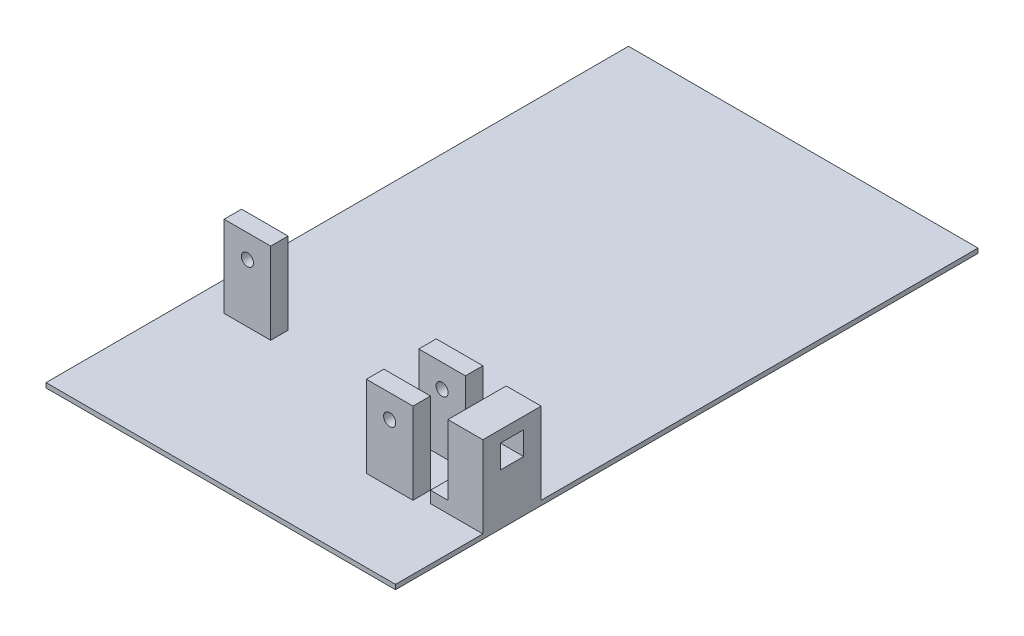
SolidWorks part; units mm, degrees
ref_plane "Front Plane" through (0, 0, 0) normal (0, 0, 1) x (1, 0, 0)
ref_plane "Top Plane" through (0, 0, 0) normal (0, 1, 0) x (1, 0, 0)
ref_plane "Right Plane" through (0, 0, 0) normal (1, 0, 0) x (0, 0, -1)
sketch "Sketch1" plane through (0, 0, 0) normal (0, 1, 0) x (1, 0, 0)
  line L0 (150, 500) -> (150, 0)
  line L1 (0, 0) -> (300, 0)
  line L2 (0, 0) -> (0, 500)
  line L3 (0, 500) -> (300, 500)
  line L4 (300, 0) -> (300, 500)
  line L5 (0, 100) -> (300, 100) construction
  line L6 (300, 125) -> (255, 125)
  line L7 (300, 125) -> (300, 75)
  line L8 (300, 75) -> (255, 75)
  line L9 (255, 125) -> (255, 75)
  line L10 (300, 125) -> (270, 125)
  line L11 (300, 125) -> (300, 75)
  line L12 (300, 75) -> (270, 75)
  line L13 (270, 125) -> (270, 75)
  point P16 (255, 100)
  dimension "D1" = 300
  dimension "D2" = 500
  dimension "D3" = 30
  dimension "D4" = 50
  dimension "D5" = 45
  dimension "D6" = 100
extrude "Boss-Extrude1" add sketch "Sketch1" along normal blind 4 contours L5 L2 L1 L0 | L2 L5 L0 L3 | L0 L5 L9 L6 L4 L3 | L9 L5 L13 L6 | L13 L5 L11 L6 | L5 L0 L1 L4 L8 L9 | L5 L9 L8 L13 | L5 L13 L8 L4 region at (223.9968, 0, -303.5828) region at (75, 0, -300) region at (220.7432, 0, -46.9595) region at (75, 0, -50) region at (262.5, 0, -112.5) region at (262.5, 0, -87.5) region at (285, 0, -112.5) region at (285, 0, -87.5)
extrude "Boss-Extrude2" add sketch "Sketch1<4>" along normal blind 10 from surface contours L9 L5 L13 L6 | L5 L9 L8 L13 | L5 L13 L8 L4 | L13 L5 L11 L6 region at (262.5, 0, -112.5) region at (262.5, 0, -87.5) region at (285, 0, -112.5) region at (285, 0, -87.5) starting at face at (150, 4, -250)
sketch "Sketch1<4>" plane through (0, 0, 0) normal (0, 1, 0) x (1, 0, 0) same geometry as "Sketch1"
extrude "Boss-Extrude3" add sketch "Sketch1<5>" along normal blind 60 from surface contours L6 L13 L8 L4 | L13 L5 L11 L6 region at (285, 0, -112.5) region at (285, 0, -87.5) starting at face at (277.5, 14, -100)
sketch "Sketch1<5>" plane through (0, 0, 0) normal (0, 1, 0) x (1, 0, 0) same geometry as "Sketch1"
sketch "Sketch15" plane through (0, 0, 0) normal (0, 1, 0) x (1, 0, 0)
  line L0 (0, 100) -> (300, 100) construction
  line L1 (245, 130) -> (205, 130)
  line L2 (245, 130) -> (245, 70)
  line L3 (245, 70) -> (205, 70)
  line L4 (205, 130) -> (205, 70)
  line L5 (245, 130) -> (205, 70) construction
  line L6 (245, 70) -> (205, 130) construction
  line L7 (255, 125) -> (255, 75) construction
  line L8 (205, 85) -> (245, 85)
  line L9 (205, 85) -> (205, 115)
  line L10 (205, 115) -> (245, 115)
  line L11 (245, 85) -> (245, 115)
  line L12 (205, 85) -> (245, 115) construction
  line L13 (205, 115) -> (245, 85) construction
  line L15 (25, 142.8667) -> (65, 142.8667)
  line L16 (25, 142.8667) -> (25, 82.8667)
  line L17 (25, 82.8667) -> (65, 82.8667)
  line L18 (65, 142.8667) -> (65, 82.8667)
  line L19 (25, 142.8667) -> (65, 82.8667) construction
  line L20 (25, 82.8667) -> (65, 142.8667) construction
  line L21 (25, 127.8667) -> (65, 127.8667)
  line L22 (25, 127.8667) -> (25, 97.8667)
  line L23 (25, 97.8667) -> (65, 97.8667)
  line L24 (65, 127.8667) -> (65, 97.8667)
  line L25 (25, 127.8667) -> (65, 97.8667) construction
  line L26 (25, 97.8667) -> (65, 127.8667) construction
  point P0 (225, 100)
  point P7 (225, 100)
  point P14 (45, 112.8667)
  point P19 (0, 0)
  point P20 (45, 112.8667)
  point P25 (45.4605, 112.8667)
  dimension "D1" = 40
  dimension "D2" = 60
  dimension "D3" = 30
  dimension "D4" = 30
  dimension "D5" = 180
  dimension "D6" = 12.8667
  dimension "D7" = 15
  dimension "D8" = 30
extrude "Boss-Extrude4" add sketch "Sketch15" along normal blind 70 from surface contours L4 L10 L2 L1 | L8 L4 L3 L2 | L16 L21 L18 L15 region at (225, 0, -122.5) region at (225, 0, -77.5) region at (45, 0, -135.3667) starting at face at (213.75, 4, -175)
sketch "Sketch16" plane through (0, 0, 0) normal (0, 0, 1) x (1, 0, 0)
  line L1 (225, 54) -> (225, 74) construction
  line L2 (205, 74) -> (245, 74) construction
  line L3 (205, 4) -> (245, 4) construction
  line L4 (45, 54) -> (45, 74) construction
  line L6 (65, 74) -> (25, 74) construction
  circle A0 centre (225, 54) radius 5.2
  circle A1 centre (45, 54) radius 5.2
  point P8 (225, 74)
  point P15 (45, 74)
  dimension "D1" = 10.4
  dimension "D2" = 50
extrude "Cut-Extrude1" cut sketch "Sketch16" against normal through all
sketch "Sketch17" plane through (0, 0, 0) normal (1, 0, 0) x (0, 0, -1)
  line L0 (100, 74) -> (100, 9.7904) construction
  line L1 (75, 74) -> (125, 74) construction
  line L3 (90, 44) -> (110, 44)
  line L4 (90, 44) -> (90, 64)
  line L5 (90, 64) -> (110, 64)
  line L6 (110, 44) -> (110, 64)
  line L7 (90, 44) -> (110, 64) construction
  line L8 (90, 64) -> (110, 44) construction
  circle A1 centre (100, 54) radius 3.25
  dimension "D1" = 20
  dimension "D2" = 6.5
  dimension "D3" = 20
  dimension "D4" = 20
extrude "Cut-Extrude2" cut sketch "Sketch17" against normal blind 26 from surface contours L0 A1 | L0 A1 | A1 L0 | L0 A1 region at (0, 54, -90.2828) region at (0, 54, -100) starting at face at (300, 20.5, -175)
extrude "Cut-Extrude3" cut sketch "Sketch17<3>" along normal through all from surface contours A1 L0 | L0 A1 region at (0, 54, -100) starting at face at (270, 44, -100)
sketch "Sketch17<3>" plane through (0, 0, 0) normal (1, 0, 0) x (0, 0, -1) same geometry as "Sketch17"
